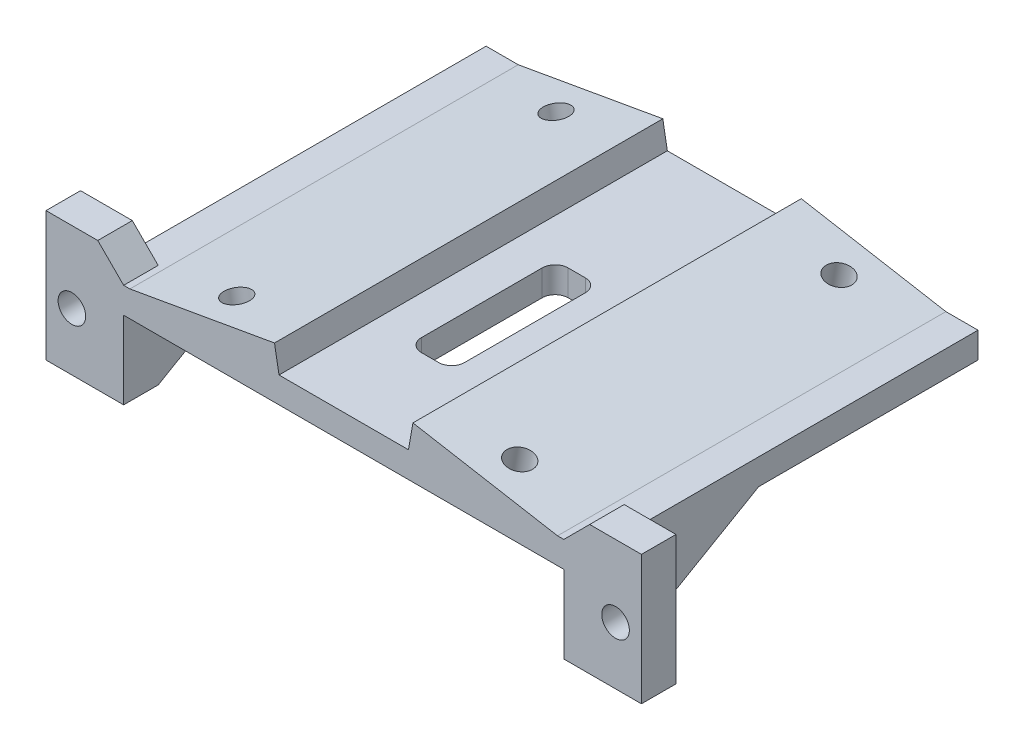
SolidWorks part; units mm, degrees
ref_plane "前视基准面" through (0, 0, 0) normal (0, 0, 1) x (1, 0, 0)
ref_plane "上视基准面" through (0, 0, 0) normal (0, 1, 0) x (1, 0, 0)
ref_plane "右视基准面" through (0, 0, 0) normal (1, 0, 0) x (0, 0, -1)
sketch "草图1" plane through (0, 0, 0) normal (0, 1, 0) x (1, 0, 0)
  line L1 (0, 0) -> (57, 0)
  line L2 (0, 0) -> (0, 45)
  line L3 (0, 45) -> (57, 45)
  line L4 (57, 0) -> (57, 45)
  dimension "D1" = 45
  dimension "D2" = 57
extrude "凸台-拉伸1" add sketch "草图1" along normal blind 3
sketch "草图2" plane through (0, 0, 0) normal (-1, 0, 0) x (0, 0, 1)
  line L0 (0, 6) -> (-4, 6)
  line L1 (-4, 6) -> (-4, -9)
  line L2 (-4, -9) -> (0, -9)
  line L3 (0, -9) -> (0, 6)
  line L4 (-45, 3) -> (0, 3) construction
  line L5 (-45, 0) -> (0, 0) construction
  line L8 (0, 3) -> (0, 0) construction
  dimension "D1" = 3
  dimension "D2" = 9
  dimension "D3" = 4
extrude "凸台-拉伸2" add sketch "草图2" along normal blind 6
sketch "草图3" plane through (57, 0, 0) normal (1, 0, 0) x (0, 0, -1)
  line L0 (0, 6) -> (0, -9)
  line L1 (0, -9) -> (4, -9)
  line L2 (4, -9) -> (4, 6)
  line L3 (4, 6) -> (0, 6)
extrude "凸台-拉伸3" add sketch "草图3" along normal blind 6
sketch "草图4" plane through (57, 0, 0) normal (-1, 0, 0) x (0, 0, 1)
  line L0 (-4, -9) -> (-19.5885, 0)
  line L1 (-4, 0) -> (-45, 0) construction
  line L2 (-19.5885, 0) -> (0, 0)
  line L3 (0, 0) -> (0, -9)
  line L4 (0, -9) -> (-4, -9)
  dimension "D1" = 30
extrude "凸台-拉伸4" add sketch "草图4" along normal blind 3
sketch "草图5" plane through (0, 0, 0) normal (1, 0, 0) x (0, 0, -1)
  line L0 (0, 0.3045) -> (0, -9)
  line L1 (0, -9) -> (4, -9)
  line L2 (4, -9) -> (19.5885, 0)
  line L3 (45, 0) -> (4, 0) construction
  line L4 (19.5885, 0) -> (0, 0)
  line M3 (4, -9) -> (4, 0)
  line M4 (4, 0) -> (0, 0)
  line M5 (0, 0) -> (0, -9)
  line M6 (0, -9) -> (4, -9)
  dimension "D1" = 30
extrude "凸台-拉伸5" add sketch "草图5" along normal blind 3 contours L2 L4 M3 | M6 M3 M4 M5 region at (0, -4.5, -2) region at (0, -3, -9.1962)
chamfer "倒角1" distance 3 angle 45 2 edges at (0, 3, -2) (57, 3, -2)
sketch "草图6" plane through (0, 0, -4) normal (0, 0, -1) x (-1, 0, 0)
  line L0 (-60, -2.3233) -> (3, -2.3233) construction
  line L1 (-63, -9) -> (-63, 6) construction
  line L2 (6, 6) -> (6, -9) construction
  circle A0 centre (3, -2.3233) radius 1.6
  circle A1 centre (-60, -2.3233) radius 1.6
  dimension "D1" = 3
  dimension "D2" = 3
extrude "切除-拉伸1" cut sketch "草图6" against normal blind 4
sketch "草图7" plane through (0, 3, 0) normal (0, 1, 0) x (1, 0, 0)
  line L0 (28, 49.7957) -> (28, -5.721) construction
  line L1 (8, 41) -> (8, 4)
  line L2 (3, 0) -> (54, 0) construction
  line L3 (0, 45) -> (0, 4) construction
  line L4 (48, 41) -> (48, 4)
  circle A0 centre (8, 41) radius 1.6
  circle A1 centre (8, 4) radius 1.6
  circle A2 centre (48, 4) radius 1.6
  circle A3 centre (48, 41) radius 1.6
  dimension "D1" = 37
  dimension "D2" = 4
  dimension "D3" = 8
extrude "切除-拉伸2" [suppressed] cut sketch "草图7" against normal blind 3 contours A3 | A2 | A0 | A1
sketch "草图8" plane through (0, 0, 0) normal (0, -1, 0) x (1, 0, 0)
  line L0 (24, -45) -> (32, -45)
  line L1 (57, -45) -> (0, -45) construction
  line L2 (32, -45) -> (32, -42)
  line L3 (32, -42) -> (24, -42)
  line L4 (24, -42) -> (24, -45)
  line L5 (28, 5.34) -> (28, -50.6665) construction
  line L6 (0, -45) -> (0, -19.5885) construction
  point P10 (32, -43.5)
  dimension "D1" = 28
  dimension "D2" = 3
  dimension "D3" = 8
  dimension "D4" = 4
extrude "凸台-拉伸6" add sketch "草图8" along normal blind 9
sketch "草图9" plane through (32, 0, 0) normal (1, 0, 0) x (0, 0, -1)
  line L0 (45, 0) -> (29.1467, 0)
  line L1 (29.1467, 0) -> (42, -9)
  line L2 (42, -9) -> (45, -9)
  line L3 (45, -9) -> (45, 0)
  dimension "D1" = 35
extrude "凸台-拉伸7" add sketch "草图9" along normal blind 3
sketch "草图10" plane through (24, 0, 0) normal (-1, 0, 0) x (0, 0, 1)
  line L0 (-45, 0) -> (-45, -9)
  line L1 (-45, -9) -> (-42, -9)
  line L2 (-42, -9) -> (-29.1467, 0)
  line L3 (-29.1467, 0) -> (-45, 0)
extrude "凸台-拉伸8" add sketch "草图10" along normal blind 3
sketch "草图11" plane through (0, 0, -42) normal (0, 0, 1) x (1, 0, 0)
  line L0 (24, -9) -> (24, 0) construction
  line L1 (32, -9) -> (24, -9) construction
  circle A0 centre (28, -4.5) radius 1.6
  dimension "D1" = 4
  dimension "D2" = 4.5
extrude "切除-拉伸3" cut sketch "草图11" against normal blind 3
sketch "草图12" plane through (0, 3, 0) normal (0, 1, 0) x (1, 0, 0)
  line L0 (28, 49.4691) -> (28, -3.816) construction
  line L1 (25.5, 27.5) -> (25.5, 10.5)
  line L2 (25.5, 10.5) -> (30.5, 10.5)
  line L3 (30.5, 10.5) -> (30.5, 27.5)
  line L4 (30.5, 27.5) -> (25.5, 27.5)
  line L5 (0, 45) -> (0, 4) construction
  line L6 (-5.009, 22.5) -> (59.3487, 22.5) construction
  line L7 (3, 0) -> (54, 0) construction
  dimension "D1" = 28
  dimension "D2" = 2.5
  dimension "D3" = 2.5
  dimension "D4" = 22.5
  dimension "D5" = 5
  dimension "D6" = 12
extrude "切除-拉伸4" cut sketch "草图12" against normal blind 3
fillet "圆角1" radius 1.5 4 edges at (30.5, 1.5, -10.5) (25.5, 1.5, -10.5) (25.5, 1.5, -27.5) (30.5, 1.5, -27.5)
ref_plane "基准面1" through (28.5, 0, 0) normal (1, 0, 0) x (0, 0, -1)
sketch "草图13" plane through (0, 3, 0) normal (0, 1, 0) x (1, 0, 0)
  line L0 (36, 45) -> (36, 0) construction
  line L1 (57, 45) -> (0, 45) construction
  line L2 (3, 0) -> (54, 0) construction
  line L3 (57, 4) -> (57, 45) construction
  dimension "D1" = 21
ref_plane "基准面2" through (34.4014, -6.0659, 0) normal (0.9848, -0.1736, 0) x (0, 0, 1)
sketch "草图14" plane through (34.4014, -6.0659, 0) normal (0.9848, -0.1736, 0) x (0, 0, 1)
  line L0 (-45, -9.2058) -> (0, -9.2058) construction
  line L1 (-45, -9.2058) -> (0, -9.2058) construction
  line L3 (-45, -9.2058) -> (0, -9.2058) construction
  line L4 (-45, -9.2058) -> (-45, -12.2058) construction
  line L5 (-45, -12.2058) -> (0, -12.2058) construction
  line L6 (0, -9.2058) -> (0, -12.2058) construction
  dimension "D1" = 3
ref_plane "基准面3" through (2.1195, 12.0203, 0) normal (0.1736, 0.9848, 0) x (0, 0, 1)
sketch "草图15" plane through (2.1195, 12.0203, 0) normal (0.1736, 0.9848, 0) x (0, 0, 1)
  line L1 (-45, 34.9321) -> (0, 34.9321)
  line L2 (-45, 34.9321) -> (-45, 52.6587)
  line L3 (-45, 52.6587) -> (0, 52.6587)
  line L4 (0, 34.9321) -> (0, 52.6587)
extrude "凸台-拉伸9" add sketch "草图15" against normal up to body separate body
sketch "草图16" plane through (2.1195, 12.0203, 0) normal (0.1736, 0.9848, 0) x (0.9848, -0.1736, 0)
  line L0 (43.4391, 45) -> (43.4391, 0) construction
  line L1 (51.946, 45) -> (34.9321, 45) construction
  line L2 (34.9321, 0) -> (51.946, 0) construction
  line L3 (51.946, 22.5) -> (43.4391, 22.5) construction
  line L4 (51.946, 45) -> (51.946, 0) construction
  circle A0 centre (43.4391, 41) radius 1.5
  circle A1 centre (43.4391, 4) radius 1.5
  dimension "D1" = 3
  dimension "D2" = 18.5
extrude "切除-拉伸5" cut sketch "草图16" against normal through all
mirror "镜向1" about plane through (28.5, 0, 0) normal (1, 0, 0) of "切除-拉伸5", "凸台-拉伸9"
